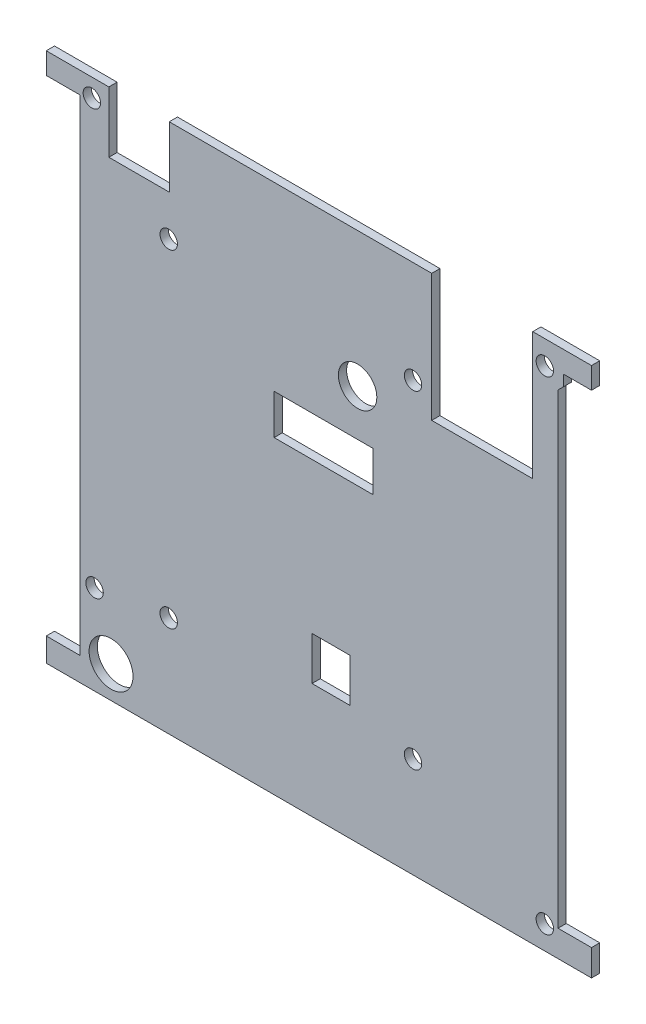
SolidWorks part; units mm, degrees
ref_plane "前视基准面" through (0, 0, 0) normal (0, 0, 1) x (1, 0, 0)
ref_plane "上视基准面" through (0, 0, 0) normal (0, 1, 0) x (1, 0, 0)
ref_plane "右视基准面" through (0, 0, 0) normal (1, 0, 0) x (0, 0, -1)
sketch "草图1" plane through (0, 0, 0) normal (0, 0, 1) x (1, 0, 0)
  line L0 (0, 4.42) -> (53.34, 4.42) construction
  line L1 (0, 0) -> (53.34, 0) construction
  line L2 (0, 0) -> (0, 68.58) construction
  line L3 (0, 68.58) -> (53.34, 68.58) construction
  line L4 (53.34, 0) -> (53.34, 68.58) construction
  line L5 (0, 64.16) -> (53.34, 64.16) construction
  line L6 (4.42, 68.58) -> (4.42, 0) construction
  line L7 (48.92, 68.58) -> (48.92, 0) construction
  line L9 (-17.88, 82.72) -> (81.42, 82.72)
  line L10 (-17.88, 82.72) -> (-17.88, -13.88)
  line L11 (-17.88, -13.88) -> (81.42, -13.88)
  line L12 (81.42, 82.72) -> (81.42, -13.88)
  circle A0 centre (48.92, 64.16) radius 1.585
  circle A1 centre (4.42, 64.16) radius 1.585
  circle A2 centre (4.42, 4.42) radius 1.585
  circle A3 centre (48.92, 4.42) radius 1.585
  circle A4 centre (-9.08, 2.42) radius 1.585
  circle A5 centre (72.92, -9.58) radius 1.585
  circle A6 centre (72.92, 78.42) radius 1.585
  circle A7 centre (-9.58, 79.42) radius 1.585
  dimension "D7" = 3.17
  dimension "D8" = 3.17
  dimension "D9" = 3.17
  dimension "D10" = 3.17
  dimension "D15" = 3.17
  dimension "D18" = 3.17
  dimension "D21" = 3.17
  dimension "D24" = 3.17
  dimension "D1" = 68.58
  dimension "D2" = 53.34
  dimension "D3" = 4.42
  dimension "D4" = 4.42
  dimension "D5" = 4.42
  dimension "D6" = 4.42
  dimension "D11" = 99.3
  dimension "D12" = 96.6
  dimension "D13" = 13.5
  dimension "D14" = 2
  dimension "D16" = 68.5
  dimension "D17" = 14
  dimension "D19" = 74
  dimension "D20" = 68.5
  dimension "D22" = 75
  dimension "D23" = 14
  dimension "D25" = 22.3
  dimension "D26" = 18.3
extrude "凸台-拉伸1" add sketch "草图1" along normal blind 1.5
sketch "草图2" plane through (0, 0, 1.5) normal (0, 0, 1) x (1, 0, 0)
  line L0 (81.42, 82.72) -> (-17.88, 82.72) construction
  line L1 (69.72, 82.72) -> (53.32, 82.72) construction
  line L2 (69.72, 82.72) -> (69.72, 60.52) construction
  line L3 (69.72, 60.52) -> (53.32, 60.52) construction
  line L4 (53.32, 82.72) -> (53.32, 60.52) construction
  line L5 (81.42, -13.88) -> (81.42, 82.72) construction
  line L6 (-17.88, 82.72) -> (-17.88, -13.88) construction
  line L7 (52.32, 82.72) -> (70.72, 82.72)
  line L8 (52.32, 82.72) -> (52.32, 59.52)
  line L9 (52.32, 59.52) -> (70.72, 59.52)
  line L10 (70.72, 82.72) -> (70.72, 59.52)
  line L11 (26.62, 48.76) -> (38.62, 48.76) construction
  line L12 (26.62, 48.76) -> (26.62, 43.46) construction
  line L13 (26.62, 43.46) -> (38.62, 43.46) construction
  line L14 (38.62, 48.76) -> (38.62, 43.46) construction
  line L15 (23.62, 49.76) -> (41.62, 49.76)
  line L16 (23.62, 49.76) -> (23.62, 42.46)
  line L17 (23.62, 42.46) -> (41.62, 42.46)
  line L18 (41.62, 49.76) -> (41.62, 42.46)
  line L19 (-17.88, 77.82) -> (-12.78, 77.82) construction
  line L20 (-17.88, 77.82) -> (-17.88, -8.58) construction
  line L21 (-17.88, -8.58) -> (-12.78, -8.58) construction
  line L22 (-12.78, 77.82) -> (-12.78, -8.58) construction
  line L23 (-17.88, -13.88) -> (81.42, -13.88) construction
  line L24 (81.42, 77.82) -> (76.32, 77.82) construction
  line L25 (81.42, 77.82) -> (81.42, -8.58) construction
  line L26 (81.42, -8.58) -> (76.32, -8.58) construction
  line L27 (76.32, 77.82) -> (76.32, -8.58) construction
  line L29 (-17.88, -9.58) -> (-11.78, -9.58)
  line L30 (-17.88, -9.58) -> (-17.88, 78.82)
  line L31 (-17.88, 78.82) -> (-11.78, 78.82)
  line L32 (-11.78, -9.58) -> (-11.78, 78.82)
  line L33 (81.42, -9.08) -> (75.32, -9.08)
  line L34 (81.42, -9.08) -> (81.42, 78.82)
  line L35 (81.42, 78.82) -> (75.32, 78.82)
  line L36 (75.32, -9.08) -> (75.32, 78.82)
  line L37 (32.52, 13.02) -> (35.42, 13.02) construction
  line L38 (32.52, 13.02) -> (32.52, 9.12) construction
  line L39 (32.52, 9.12) -> (35.42, 9.12) construction
  line L40 (35.42, 13.02) -> (35.42, 9.12) construction
  line L41 (30.52, 15.02) -> (37.42, 15.02)
  line L42 (30.52, 15.02) -> (30.52, 7.12)
  line L43 (30.52, 7.12) -> (37.42, 7.12)
  line L44 (37.42, 15.02) -> (37.42, 7.12)
  line L45 (-6.48, 82.72) -> (3.52, 82.72) construction
  line L46 (-6.48, 82.72) -> (-6.48, 72.62) construction
  line L47 (-6.48, 72.62) -> (3.52, 72.62) construction
  line L48 (3.52, 82.72) -> (3.52, 72.62) construction
  line L49 (-6.48, 82.72) -> (4.52, 82.72)
  line L50 (-6.48, 82.72) -> (-6.48, 71.62)
  line L51 (-6.48, 71.62) -> (4.52, 71.62)
  line L52 (4.52, 82.72) -> (4.52, 71.62)
  circle A0 centre (38.82, 58.16) radius 3.5
  circle A1 centre (48.92, 64.16) radius 1.585 construction
  circle A2 centre (-6.08, -8.08) radius 4
  circle A3 centre (48.92, 4.42) radius 1.585 construction
  point P45 (78.87, 77.82)
  dimension "D9" = 7
  dimension "D32" = 8
  dimension "D1" = 11.7
  dimension "D2" = 16.4
  dimension "D3" = 22.2
  dimension "D4" = 1
  dimension "D5" = 1
  dimension "D6" = 1
  dimension "D7" = 10.1
  dimension "D8" = 6
  dimension "D10" = 10.3
  dimension "D11" = 15.4
  dimension "D12" = 12
  dimension "D13" = 5.3
  dimension "D14" = 3
  dimension "D15" = 3
  dimension "D16" = 1
  dimension "D17" = 1
  dimension "D18" = 4.9
  dimension "D19" = 4.9
  dimension "D20" = 5.1
  dimension "D21" = 5.1
  dimension "D22" = 5.3
  dimension "D23" = 5.3
  dimension "D24" = 1
  dimension "D25" = 1
  dimension "D26" = 1
  dimension "D27" = 1
  dimension "D28" = 1
  dimension "D29" = 1
  dimension "D30" = 11.8
  dimension "D31" = 5.8
  dimension "D33" = 13.5
  dimension "D34" = 4.7
  dimension "D35" = 2.9
  dimension "D36" = 3.9
  dimension "D37" = 2
  dimension "D38" = 2
  dimension "D39" = 2
  dimension "D40" = 2
  dimension "D41" = 11.4
  dimension "D42" = 10
  dimension "D43" = 10.1
  dimension "D44" = 0
  dimension "D45" = 1
  dimension "D46" = 1
extrude "切除-拉伸1" cut sketch "草图2" against normal through all
sketch "草图3" plane through (0, 0, 1.5) normal (0, 0, 1) x (1, 0, 0)
  line L1 (75.32, 78.82) -> (76.32, 78.82)
  line L2 (75.32, 78.82) -> (75.32, 76.82)
  line L4 (76.32, 78.82) -> (76.32, 76.82)
  line L7 (76.32, 76.82) -> (75.32, 76.82)
  dimension "D2" = 2
  dimension "D3" = 1
extrude "凸台-拉伸2" add sketch "草图3" against normal up to surface (1.5 mm away) contours L2 L7 L4 L1 up to face at (32.62, 46.11, 0)
chamfer "倒角1" distance 1 angle 45 1 edges at (75.32, 76.82, 0.75)
